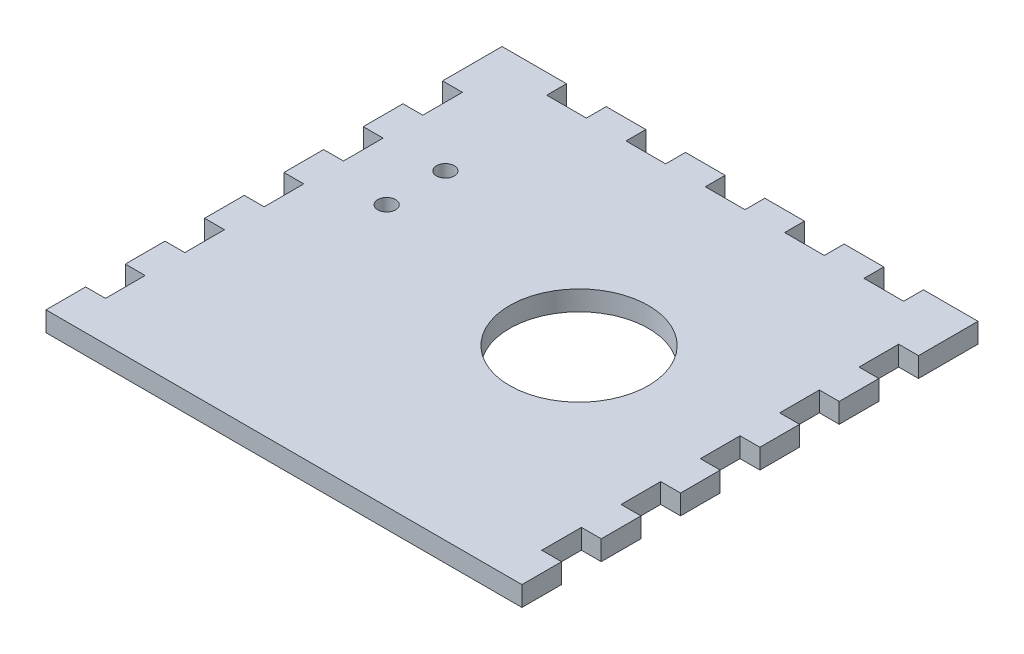
SolidWorks part; units mm, degrees
ref_plane "Front Plane" through (0, 0, 0) normal (0, 0, 1) x (1, 0, 0)
ref_plane "Top Plane" through (0, 0, 0) normal (0, 1, 0) x (1, 0, 0)
ref_plane "Right Plane" through (0, 0, 0) normal (1, 0, 0) x (0, 0, -1)
sketch "Sketch1" plane through (0, 0, 0) normal (0, 1, 0) x (1, 0, 0)
  line L1 (-139.7, -139.7) -> (139.7, -139.7)
  line L2 (-139.7, -139.7) -> (-139.7, 139.7)
  line L3 (-139.7, 139.7) -> (139.7, 139.7)
  line L4 (139.7, -139.7) -> (139.7, 139.7)
  line L5 (-139.7, -139.7) -> (139.7, 139.7) construction
  line L6 (-139.7, 139.7) -> (139.7, -139.7) construction
  point P0 (0, 0)
  dimension "D1" = 279.4
  dimension "D2" = 279.4
extrude "Boss-Extrude1" add sketch "Sketch1" along normal blind 12.7
sketch "Sketch2" plane through (139.7, 0, 0) normal (1, 0, 0) x (0, 0, -1)
  line L0 (-139.7, 12.7) -> (139.7, 12.7) construction
  line L1 (-139.7, 0) -> (-114.3, 0)
  line L2 (-139.7, 0) -> (-139.7, 12.7)
  line L3 (-139.7, 12.7) -> (-114.3, 12.7)
  line L4 (-114.3, 0) -> (-114.3, 12.7)
  dimension "D1" = 25.4
extrude "Boss-Extrude2" add sketch "Sketch2" along normal blind 12.7
pattern_linear "LPattern1" count 6 spacing 50.8 along (0, 0, -1) of "Boss-Extrude2"
mirror "Mirror1" about plane through (0, 0, 0) normal (1, 0, 0) of "LPattern1"
sketch "Sketch3" plane through (0, 0, -139.7) normal (0, 0, -1) x (-1, 0, 0)
  line L0 (-152.4, 12.7) -> (152.4, 12.7) construction
  line L1 (-142.875, 12.7) -> (-117.475, 12.7)
  line L2 (-142.875, 12.7) -> (-142.875, 0)
  line L3 (-142.875, 0) -> (-117.475, 0)
  line L4 (-117.475, 12.7) -> (-117.475, 0)
  line L5 (-152.4, 0) -> (152.4, 0) construction
  line L6 (-152.4, 0) -> (-152.4, 12.7) construction
  dimension "D1" = 9.525
  dimension "D2" = 25.4
extrude "Boss-Extrude3" add sketch "Sketch3" along normal blind 12.7
pattern_linear "LPattern2" count 6 spacing 50.8 along (-1, 0, 0) of "Boss-Extrude3"
sketch "Sketch5" plane through (0, 0, -139.7) normal (0, 0, -1) x (-1, 0, 0)
  line L6 (160.655, 0) -> (-160.655, 0) construction
  line L7 (-152.4, 12.7) -> (-135.3964, 12.7)
  line L8 (-152.4, 12.7) -> (-152.4, 0)
  line L9 (-152.4, 0) -> (-135.3964, 0)
  line L10 (-135.3964, 12.7) -> (-135.3964, 0)
extrude "Boss-Extrude4" add sketch "Sketch5" along normal blind 12.7
mirror "Mirror2" about plane through (0, 0, 0) normal (1, 0, 0) of "Boss-Extrude4"
sketch "Sketch6" plane through (0, 12.7, 0) normal (0, 1, 0) x (1, 0, 0)
  line L0 (66.675, 139.7) -> (41.275, 139.7) construction
  line L1 (139.7, -12.7) -> (139.7, 12.7) construction
  circle A0 centre (38.1, 11.176) radius 44.45
  dimension "D1" = 128.524
  dimension "D2" = 101.6
extrude "Cut-Extrude1" cut sketch "Sketch6" against normal through all
sketch "Sketch7" plane through (0, 12.7, 0) normal (0, 1, 0) x (1, 0, 0)
  line L0 (-139.7, 63.5) -> (-139.7, 38.1) construction
  line L1 (-139.7, 114.3) -> (-139.7, 88.9) construction
  line L2 (-85.725, 139.7) -> (-111.125, 139.7) construction
  circle A0 centre (-101.6, 65.278) radius 5.715
  circle A1 centre (-101.6, 27.686) radius 5.715
  dimension "D1" = 11.43
  dimension "D2" = 11.43
  dimension "D3" = 38.1
  dimension "D4" = 38.1
  dimension "D5" = 37.592
  dimension "D6" = 74.422
extrude "Cut-Extrude2" cut sketch "Sketch7" against normal through all
